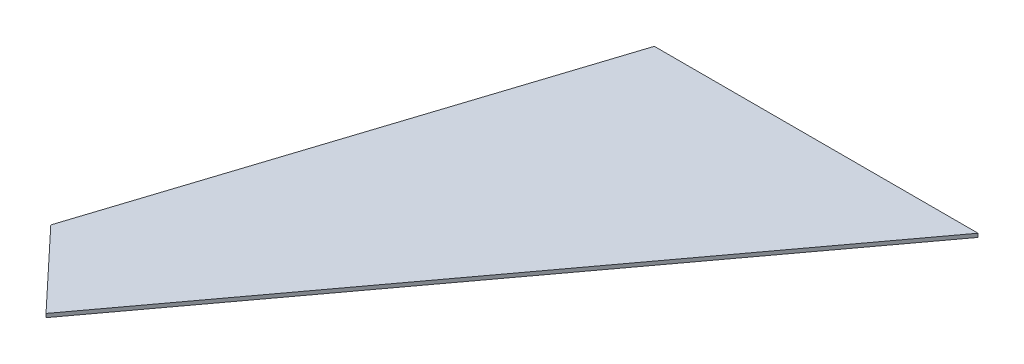
SolidWorks part; units mm, degrees
ref_plane "Front Plane" through (0, 0, 0) normal (0, 0, 1) x (1, 0, 0)
ref_plane "Top Plane" through (0, 0, 0) normal (0, 1, 0) x (1, 0, 0)
ref_plane "Right Plane" through (0, 0, 0) normal (1, 0, 0) x (0, 0, -1)
sketch "Sketch1" plane through (0, 0, 0) normal (0, 1, 0) x (1, 0, 0)
  line L1 (0, 0) -> (500, 0)
  line L2 (0, 0) -> (0, -500)
  line L3 (0, -500) -> (500, -500)
  line L4 (500, 0) -> (500, -500)
extrude "Boss-Extrude1" add sketch "Sketch1" along normal blind 2.9972
sketch "Sketch2" plane through (0, 0, 0) normal (0, -1, 0) x (1, 0, 0)
  line L0 (384.3751, 0) -> (120.0994, 0)
  line L1 (500, 0) -> (0, 0) construction
  line L2 (120.0994, 0) -> (0, 372.6892) construction
  line L3 (120.0994, 0) -> (0, 372.6892)
  line L4 (0, 372.6892) -> (60.6294, 437.2268)
  line L5 (60.6294, 437.2268) -> (384.3751, 0)
extrude "Cut-Extrude1" cut sketch "Sketch2" against normal through all flip side to cut
